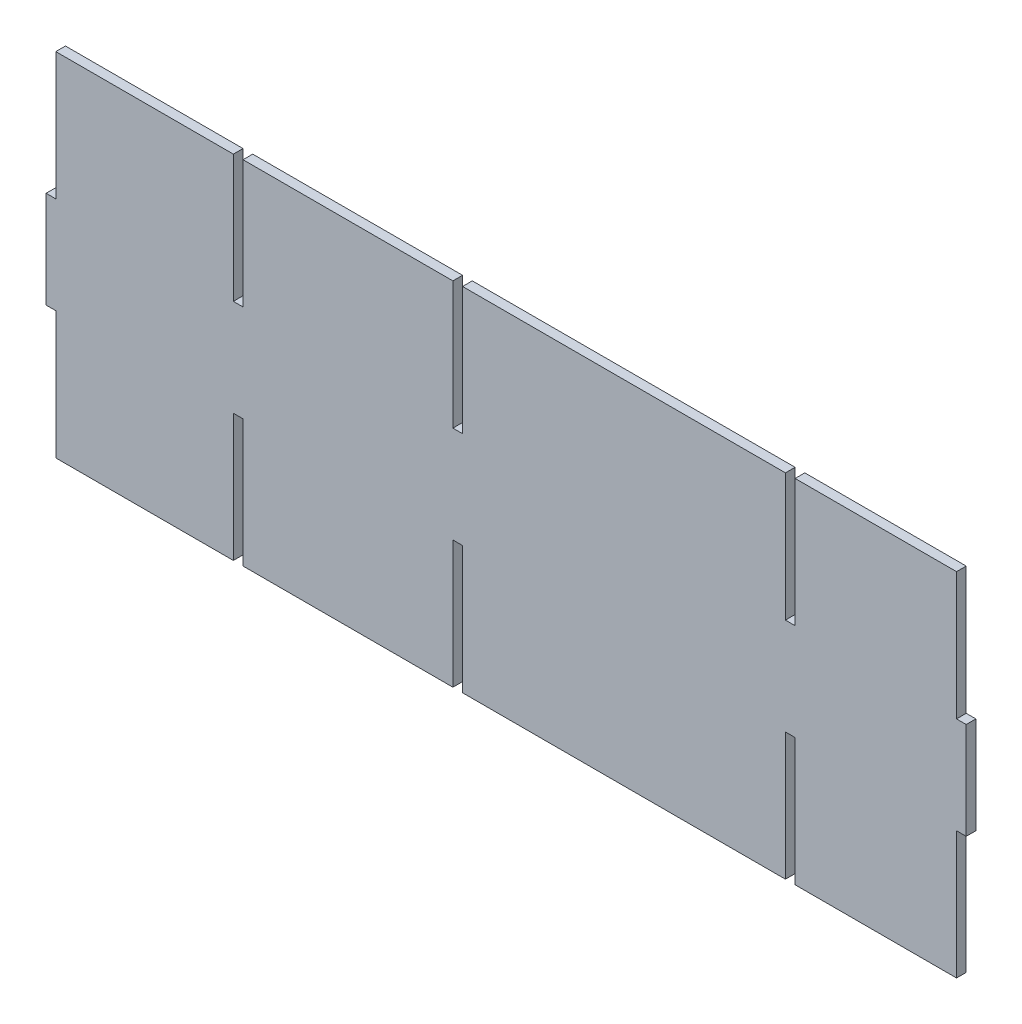
SolidWorks part; units mm, degrees
ref_plane "Front Plane" through (0, 0, 0) normal (0, 0, 1) x (1, 0, 0)
ref_plane "Top Plane" through (0, 0, 0) normal (0, 1, 0) x (1, 0, 0)
ref_plane "Right Plane" through (0, 0, 0) normal (1, 0, 0) x (0, 0, -1)
sketch "Sketch1" plane through (0, 0, 0) normal (0, 0, 1) x (1, 0, 0)
  line L0 (0, 0) -> (3, 0)
  line L1 (3, 0) -> (3, -39.5)
  line L2 (3, -39.5) -> (58, -39.5)
  line L3 (58, -39.5) -> (58, 0)
  line L4 (58, 0) -> (61, 0)
  line L5 (61, 0) -> (61, -39.5)
  line L6 (61, -39.5) -> (126, -39.5)
  line L7 (126, -39.5) -> (126, 0)
  line L8 (126, 0) -> (129, 0)
  line L9 (129, 0) -> (129, -39.5)
  line L10 (129, -39.5) -> (229, -39.5)
  line L11 (229, -39.5) -> (229, 0)
  line L12 (229, 0) -> (232, 0)
  line L13 (232, 0) -> (232, -39.5)
  line L14 (232, -39.5) -> (282, -39.5)
  line L15 (282, -39.5) -> (282, 0)
  line L16 (282, 0) -> (285, 0)
  line L17 (285, 0) -> (285, 30)
  line L18 (285, 15) -> (0, 15) construction
  line L19 (0, 30) -> (0, 0)
  line L20 (282, 30) -> (285, 30)
  line L21 (282, 69.5) -> (282, 30)
  line L22 (232, 69.5) -> (282, 69.5)
  line L23 (232, 30) -> (232, 69.5)
  line L24 (229, 30) -> (232, 30)
  line L25 (229, 69.5) -> (229, 30)
  line L26 (129, 69.5) -> (229, 69.5)
  line L27 (129, 30) -> (129, 69.5)
  line L28 (126, 30) -> (129, 30)
  line L29 (126, 69.5) -> (126, 30)
  line L30 (61, 69.5) -> (126, 69.5)
  line L31 (61, 30) -> (61, 69.5)
  line L32 (58, 30) -> (61, 30)
  line L33 (58, 69.5) -> (58, 30)
  line L34 (3, 69.5) -> (58, 69.5)
  line L35 (3, 30) -> (3, 69.5)
  line L36 (0, 30) -> (3, 30)
  point P20 (0, 0)
  point P22 (0, 0)
  point P23 (0, 0)
  point P24 (0, 0)
  dimension "D1" = 15
  dimension "D2" = 54.5
  dimension "D3" = 3
  dimension "D4" = 3
  dimension "D5" = 3
  dimension "D6" = 3
  dimension "D7" = 15
  dimension "D8" = 3
  dimension "D9" = 55
  dimension "D10" = 65
  dimension "D11" = 100
  dimension "D12" = 50
extrude "Boss-Extrude1" add sketch "Sketch1" along normal blind 3
